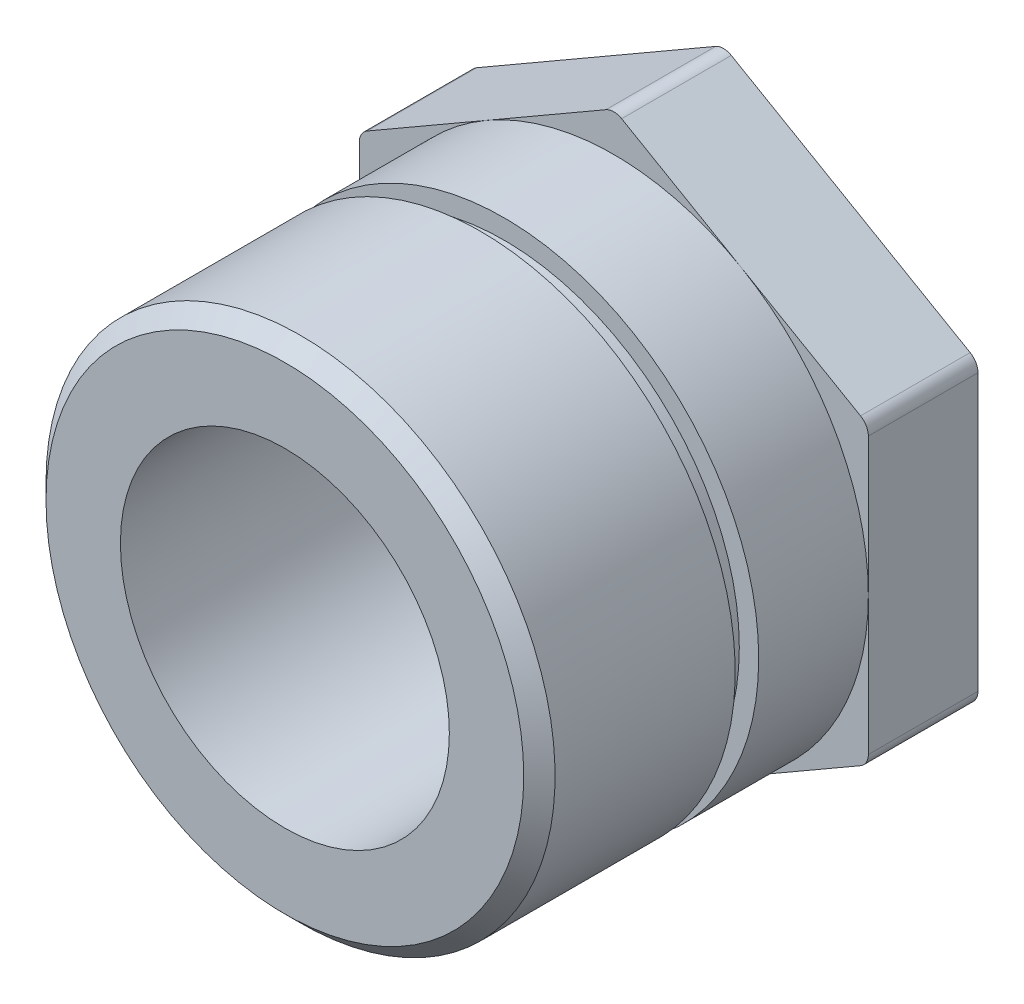
SolidWorks part; units mm, degrees
ref_plane "Front Plane" through (0, 0, 0) normal (0, 0, 1) x (1, 0, 0)
ref_plane "Top Plane" through (0, 0, 0) normal (0, 1, 0) x (1, 0, 0)
ref_plane "Right Plane" through (0, 0, 0) normal (1, 0, 0) x (0, 0, -1)
sketch "Sketch1" plane through (0, 0, 0) normal (0, 0, 1) x (1, 0, 0)
  circle A0 centre (0, 0) radius 32.5
extrude "Boss-Extrude1" add sketch "Sketch1" along normal blind 42
cosmetic thread "Cosmetic Thread1" parameters "D1"=25, "D2"=59.61
sketch "Sketch2" plane through (0, 0, 42) normal (0, 0, 1) x (1, 0, 0)
  circle A0 centre (0, 0) radius 30
  circle A2 centre (0, 0) radius 32.5
extrude "Boss-Extrude5" add sketch "Sketch2" along normal blind 3 from offset 28 offset against normal yes
ref_plane "Plane1" through (0, 0, 42) normal (0, 0, 1) x (1, 0, 0)
sketch "Sketch6" plane through (0, 0, 42) normal (0, 0, 1) x (1, 0, 0)
  circle A0 centre (0, 0) radius 32.5
  circle A1 centre (0, 0) radius 30.0241
extrude "Cut-Extrude1" cut sketch "Sketch6" along normal blind 3 from offset 28 offset against normal yes
sketch "Sketch7" plane through (0, 0, 0) normal (0, 0, -1) x (-1, 0, 0)
  line L1 (0, 37.5278) -> (-32.5, 18.7639)
  line L2 (-32.5, 18.7639) -> (-32.5, -18.7639)
  line L3 (-32.5, -18.7639) -> (0, -37.5278)
  line L4 (0, -37.5278) -> (32.5, -18.7639)
  line L5 (32.5, -18.7639) -> (32.5, 18.7639)
  line L6 (32.5, 18.7639) -> (0, 37.5278)
  circle A0 centre (0, 0) radius 32.5 construction
  circle A1 centre (0, 0) radius 32.5 construction
extrude "Boss-Extrude6" add sketch "Sketch7" along normal blind 14
fillet "Fillet1" radius 2 6 edges at (-32.5, 18.7639, -7) (0, -37.5278, -7) (32.5, -18.7639, -7) (32.5, 18.7639, -7) (0, 37.5278, -7) (-32.5, -18.7639, -7)
chamfer "Chamfer1" distance 2 angle 45 1 edges at (32.5, 0, 42)
sketch "Sketch8" plane through (0, 0, 42) normal (0, 0, 1) x (1, 0, 0)
  circle A0 centre (0, 0) radius 21
extrude "Cut-Extrude2" cut sketch "Sketch8" against normal through all
